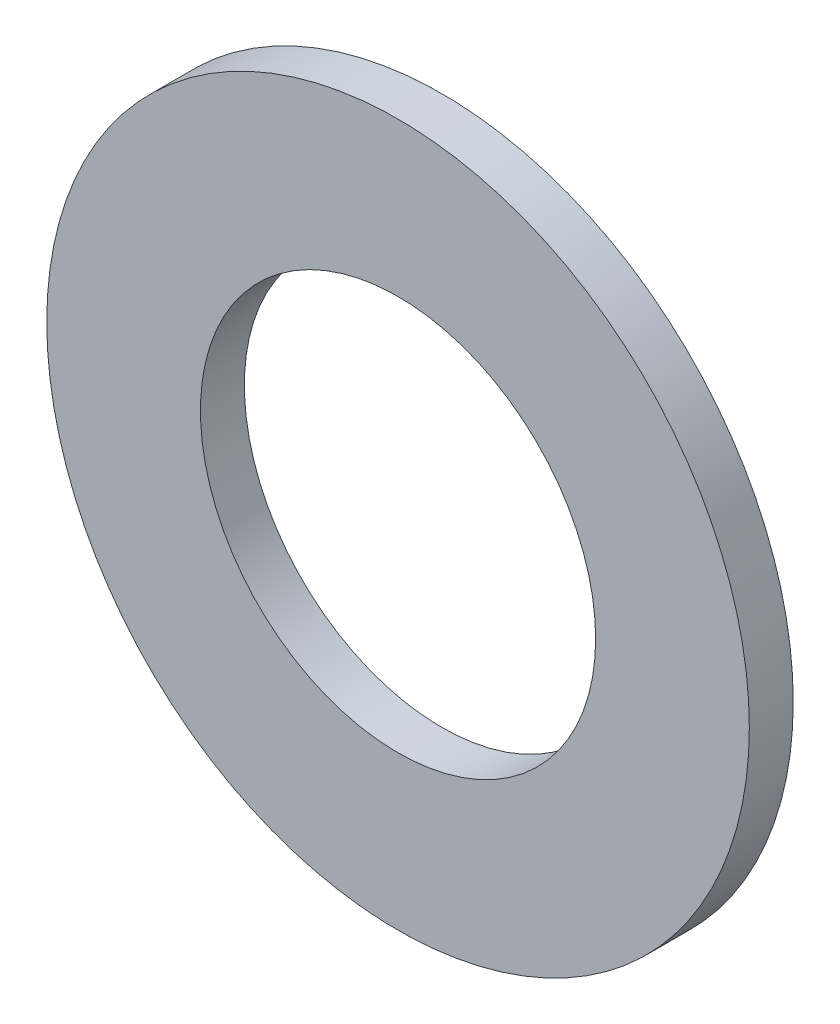
SolidWorks part; units mm, degrees
material "Латунь"
ref_plane "Спереди" through (0, 0, 0) normal (0, 0, 1) x (1, 0, 0)
ref_plane "Сверху" through (0, 0, 0) normal (0, 1, 0) x (1, 0, 0)
ref_plane "Справа" through (0, 0, 0) normal (1, 0, 0) x (0, 0, -1)
sketch "Эскиз1" plane through (0, 0, 0) normal (0, 0, 1) x (1, 0, 0)
  circle A0 centre (0, 0) radius 8
  circle A1 centre (0, 0) radius 4.5
  dimension "D1" = 9
  dimension "D2" = 16
extrude "Бобышка-Вытянуть1" add sketch "Эскиз1" along normal blind 1
equation "\"Внутренний диаметр\" = 8  '!!!"
equation "\"Внешний диаметр\" = 16"
equation "\"Толщина\" = 1  'Толщина шайбы между пластиной прижима и несущей пластиной"
equation "\"D1@Эскиз1\"=\"Внутренний диаметр\"+1"
equation "\"D1@Бобышка-Вытянуть1\"=\"Толщина\""
equation "\"D2@Эскиз1\"=\"Внешний диаметр\""
